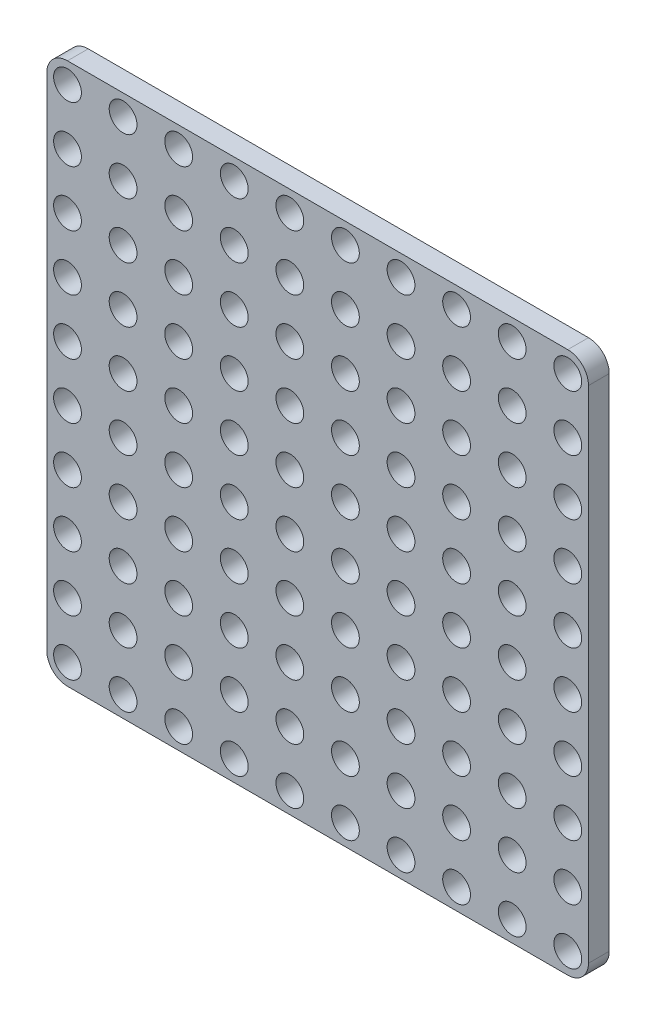
SolidWorks part; units mm, degrees
material "ABS"
ref_plane "Ebene vorne" through (0, 0, 0) normal (0, 0, 1) x (1, 0, 0)
ref_plane "Ebene oben" through (0, 0, 0) normal (0, 1, 0) x (1, 0, 0)
ref_plane "Ebene rechts" through (0, 0, 0) normal (1, 0, 0) x (0, 0, -1)
sketch "Skizze1" plane through (0, 0, 0) normal (0, 0, 1) x (1, 0, 0)
  line L0 (5, 5) -> (5, 18.4) construction
  line L1 (0, 0) -> (130.6, 0)
  line L2 (0, 0) -> (0, 130.6)
  line L3 (0, 130.6) -> (130.6, 130.6)
  line L4 (130.6, 0) -> (130.6, 130.6)
  line L5 (5, 5) -> (18.4, 5) construction
  circle A0 centre (5, 5) radius 3.35
  circle A1 centre (5, 18.4) radius 3.35
  circle A2 centre (5, 31.8) radius 3.35
  circle A3 centre (5, 45.2) radius 3.35
  circle A4 centre (5, 58.6) radius 3.35
  circle A5 centre (5, 72) radius 3.35
  circle A6 centre (5, 85.4) radius 3.35
  circle A7 centre (5, 98.8) radius 3.35
  circle A8 centre (5, 112.2) radius 3.35
  circle A9 centre (5, 125.6) radius 3.35
  circle A10 centre (18.4, 18.4) radius 3.35
  circle A11 centre (18.4, 31.8) radius 3.35
  circle A12 centre (18.4, 45.2) radius 3.35
  circle A13 centre (18.4, 58.6) radius 3.35
  circle A14 centre (18.4, 72) radius 3.35
  circle A15 centre (18.4, 85.4) radius 3.35
  circle A16 centre (18.4, 98.8) radius 3.35
  circle A17 centre (18.4, 112.2) radius 3.35
  circle A18 centre (18.4, 125.6) radius 3.35
  circle A19 centre (31.8, 18.4) radius 3.35
  circle A20 centre (31.8, 31.8) radius 3.35
  circle A21 centre (31.8, 45.2) radius 3.35
  circle A22 centre (31.8, 58.6) radius 3.35
  circle A23 centre (31.8, 72) radius 3.35
  circle A24 centre (31.8, 85.4) radius 3.35
  circle A25 centre (31.8, 98.8) radius 3.35
  circle A26 centre (31.8, 112.2) radius 3.35
  circle A27 centre (31.8, 125.6) radius 3.35
  circle A28 centre (45.2, 18.4) radius 3.35
  circle A29 centre (45.2, 31.8) radius 3.35
  circle A30 centre (45.2, 45.2) radius 3.35
  circle A31 centre (45.2, 58.6) radius 3.35
  circle A32 centre (45.2, 72) radius 3.35
  circle A33 centre (45.2, 85.4) radius 3.35
  circle A34 centre (45.2, 98.8) radius 3.35
  circle A35 centre (45.2, 112.2) radius 3.35
  circle A36 centre (45.2, 125.6) radius 3.35
  circle A37 centre (58.6, 18.4) radius 3.35
  circle A38 centre (58.6, 31.8) radius 3.35
  circle A39 centre (58.6, 45.2) radius 3.35
  circle A40 centre (58.6, 58.6) radius 3.35
  circle A41 centre (58.6, 72) radius 3.35
  circle A42 centre (58.6, 85.4) radius 3.35
  circle A43 centre (58.6, 98.8) radius 3.35
  circle A44 centre (58.6, 112.2) radius 3.35
  circle A45 centre (58.6, 125.6) radius 3.35
  circle A46 centre (72, 18.4) radius 3.35
  circle A47 centre (72, 31.8) radius 3.35
  circle A48 centre (72, 45.2) radius 3.35
  circle A49 centre (72, 58.6) radius 3.35
  circle A50 centre (72, 72) radius 3.35
  circle A51 centre (72, 85.4) radius 3.35
  circle A52 centre (72, 98.8) radius 3.35
  circle A53 centre (72, 112.2) radius 3.35
  circle A54 centre (72, 125.6) radius 3.35
  circle A55 centre (85.4, 18.4) radius 3.35
  circle A56 centre (85.4, 31.8) radius 3.35
  circle A57 centre (85.4, 45.2) radius 3.35
  circle A58 centre (85.4, 58.6) radius 3.35
  circle A59 centre (85.4, 72) radius 3.35
  circle A60 centre (85.4, 85.4) radius 3.35
  circle A61 centre (85.4, 98.8) radius 3.35
  circle A62 centre (85.4, 112.2) radius 3.35
  circle A63 centre (85.4, 125.6) radius 3.35
  circle A64 centre (98.8, 18.4) radius 3.35
  circle A65 centre (98.8, 31.8) radius 3.35
  circle A66 centre (98.8, 45.2) radius 3.35
  circle A67 centre (98.8, 58.6) radius 3.35
  circle A68 centre (98.8, 72) radius 3.35
  circle A69 centre (98.8, 85.4) radius 3.35
  circle A70 centre (98.8, 98.8) radius 3.35
  circle A71 centre (98.8, 112.2) radius 3.35
  circle A72 centre (98.8, 125.6) radius 3.35
  circle A73 centre (112.2, 18.4) radius 3.35
  circle A74 centre (112.2, 31.8) radius 3.35
  circle A75 centre (112.2, 45.2) radius 3.35
  circle A76 centre (112.2, 58.6) radius 3.35
  circle A77 centre (112.2, 72) radius 3.35
  circle A78 centre (112.2, 85.4) radius 3.35
  circle A79 centre (112.2, 98.8) radius 3.35
  circle A80 centre (112.2, 112.2) radius 3.35
  circle A81 centre (112.2, 125.6) radius 3.35
  circle A82 centre (125.6, 18.4) radius 3.35
  circle A83 centre (125.6, 31.8) radius 3.35
  circle A84 centre (125.6, 45.2) radius 3.35
  circle A85 centre (125.6, 58.6) radius 3.35
  circle A86 centre (125.6, 72) radius 3.35
  circle A87 centre (125.6, 85.4) radius 3.35
  circle A88 centre (125.6, 98.8) radius 3.35
  circle A89 centre (125.6, 112.2) radius 3.35
  circle A90 centre (125.6, 125.6) radius 3.35
  circle A91 centre (18.4, 5) radius 3.35
  circle A92 centre (31.8, 5) radius 3.35
  circle A93 centre (45.2, 5) radius 3.35
  circle A94 centre (58.6, 5) radius 3.35
  circle A95 centre (72, 5) radius 3.35
  circle A96 centre (85.4, 5) radius 3.35
  circle A97 centre (98.8, 5) radius 3.35
  circle A98 centre (112.2, 5) radius 3.35
  circle A99 centre (125.6, 5) radius 3.35
  dimension "D1" = 10
  dimension "D3" = 6.7
  dimension "D2" = 10
  dimension "D4" = 13.4
  dimension "D5" = 13.4
  dimension "D6" = 5
  dimension "D7" = 5
  dimension "D8" = 5
  dimension "D9" = 5
extrude "Boss-Extrude1" add sketch "Skizze1" along normal blind 5
fillet "Fillet2" radius 5 4 edges at (0, 0, 2.5) (0, 130.6, 2.5) (130.6, 130.6, 2.5) (130.6, 0, 2.5)
